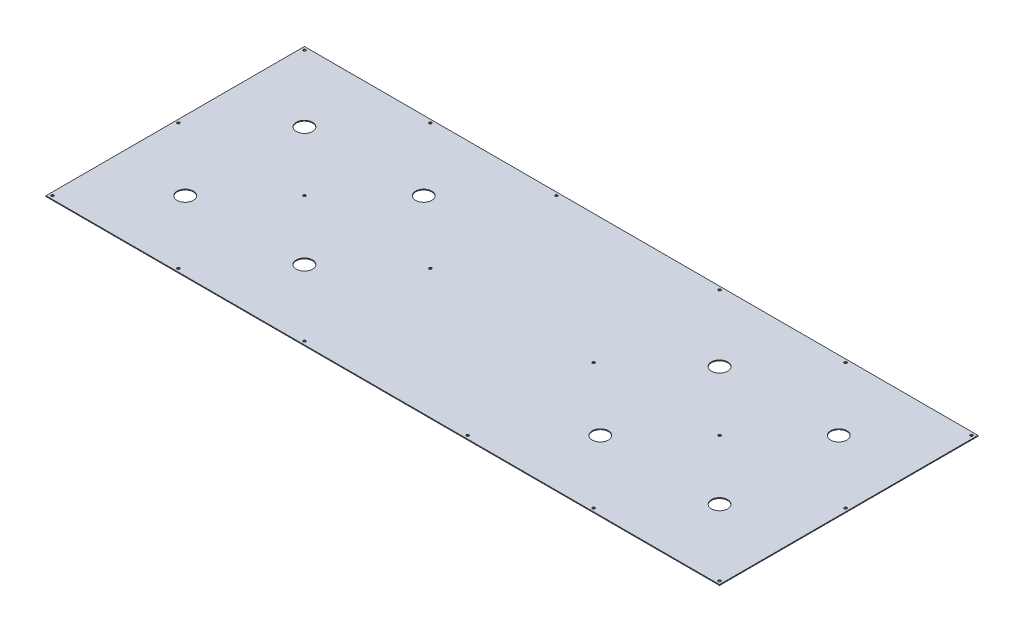
SolidWorks part; units mm, degrees
ref_plane "Front Plane" through (0, 0, 0) normal (0, 0, 1) x (1, 0, 0)
ref_plane "Top Plane" through (0, 0, 0) normal (0, 1, 0) x (1, 0, 0)
ref_plane "Right Plane" through (0, 0, 0) normal (1, 0, 0) x (0, 0, -1)
sketch "main_plate" plane through (0, 0, 0) normal (0, 1, 0) x (1, 0, 0)
  line L1 (-417, 160) -> (417, 160)
  line L2 (-417, 160) -> (-417, -160)
  line L3 (-417, -160) -> (417, -160)
  line L4 (417, 160) -> (417, -160)
  line L5 (-417, 160) -> (417, -160) construction
  line L6 (-417, -160) -> (417, 160) construction
  point P0 (0, 0)
  dimension "D1" = 320
  dimension "D2" = 834
extrude "Boss-Extrude1" add sketch "main_plate" along normal blind 1.016
sketch "main_holes" plane through (0, 1.016, 0) normal (0, 1, 0) x (1, 0, 0)
  line L0 (-417, 160) -> (-417, -160) construction
  line L1 (417, 160) -> (-417, 160) construction
  line L2 (-417, 0) -> (417, 0) construction
  line L3 (417, -160) -> (417, 160) construction
  line L4 (-417, -160) -> (417, -160) construction
  line L5 (0, 160) -> (0, -160) construction
  circle A0 centre (-413, 156) radius 1.6
  circle A6 centre (-257, 156) radius 1.6
  circle A7 centre (-101, 156) radius 1.6
  circle A8 centre (-257, 0) radius 1.6
  circle A9 centre (-101, 0) radius 1.6
  circle A10 centre (-257, -156) radius 1.6
  circle A11 centre (-101, -156) radius 1.6
  circle A12 centre (-413, 0) radius 1.6
  circle A13 centre (-413, -156) radius 1.6
  circle A18 centre (413, -156) radius 1.6
  circle A19 centre (413, 0) radius 1.6
  circle A20 centre (101, -156) radius 1.6
  circle A21 centre (257, -156) radius 1.6
  circle A22 centre (101, 0) radius 1.6
  circle A23 centre (257, 0) radius 1.6
  circle A24 centre (101, 156) radius 1.6
  circle A25 centre (257, 156) radius 1.6
  circle A28 centre (413, 156) radius 1.6
  dimension "D3" = 3.2
  dimension "D1" = 4
  dimension "D2" = 4
  dimension "D4" = 3
  dimension "D5" = 3
extrude "Cut-Extrude1" cut sketch "main_holes" against normal through all
sketch "sma" plane through (0, 1.016, 0) normal (0, 1, 0) x (1, 0, 0)
  line L0 (0, 160) -> (0, -160) construction
  line L1 (417, 160) -> (-417, 160) construction
  line L2 (-417, -160) -> (417, -160) construction
  circle A0 centre (-330.8187, 73.8188) radius 10
  circle A1 centre (-183.1812, 73.8188) radius 10
  circle A2 centre (-183.1812, -73.8187) radius 10
  circle A3 centre (-330.8187, -73.8187) radius 10
  circle A4 centre (-257, 0) radius 1.6 construction
  circle A5 centre (330.8187, -73.8187) radius 10
  circle A6 centre (183.1812, -73.8187) radius 10
  circle A7 centre (183.1812, 73.8188) radius 10
  circle A8 centre (330.8187, 73.8188) radius 10
  dimension "D1" = 20
  dimension "D4" = 73.8188
  dimension "D5" = 73.8188
  dimension "D2" = 2
  dimension "D3" = 2
extrude "Cut-Extrude2" cut sketch "sma" against normal through all
